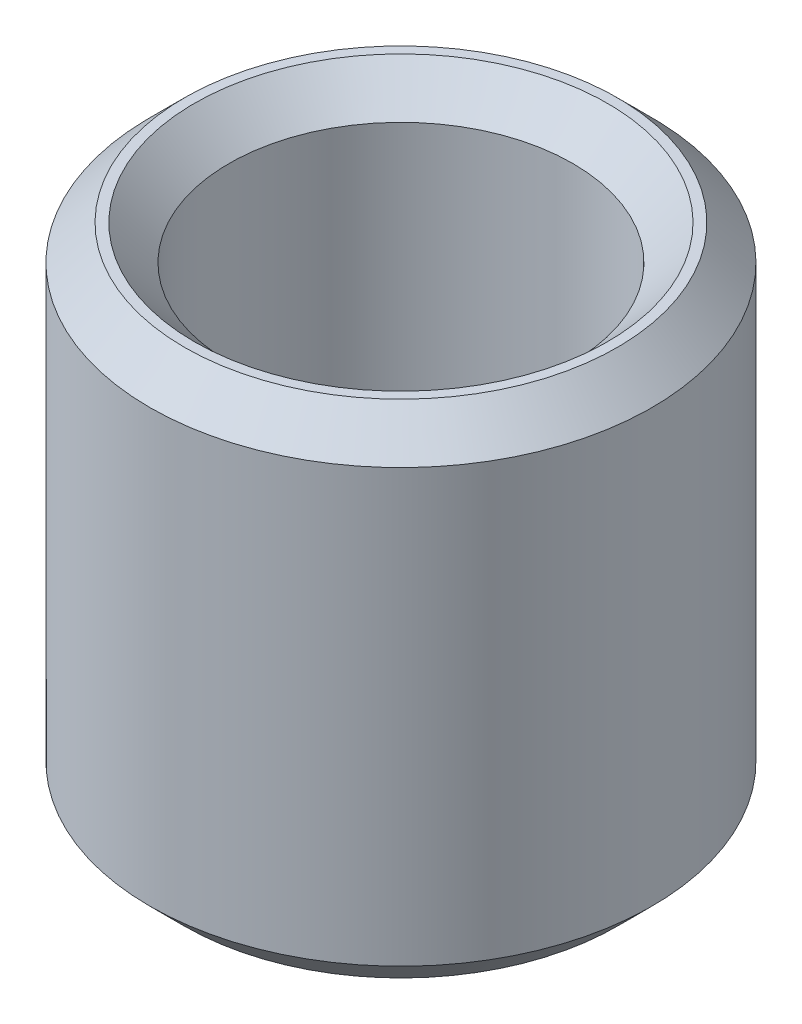
SolidWorks part; units mm, degrees
ref_plane "Front Plane" through (0, 0, 0) normal (0, 0, 1) x (1, 0, 0)
ref_plane "Top Plane" through (0, 0, 0) normal (0, 1, 0) x (1, 0, 0)
ref_plane "Right Plane" through (0, 0, 0) normal (1, 0, 0) x (0, 0, -1)
sketch "Sketch1" plane through (0, 0, 0) normal (0, 1, 0) x (1, 0, 0)
  circle A0 centre (0, 0) radius 25
  dimension "SLEEVE_OD" = 50
extrude "Boss-Extrude1" add sketch "Sketch1" along normal blind 49.9193
sketch "Sketch2" plane through (0, 0, 0) normal (0, 1, 0) x (1, 0, 0)
  circle A0 centre (0, 0) radius 17.1136
  dimension "BORE_D" = 34.2271
extrude "Cut-Extrude1" cut sketch "Sketch2" along normal through all
chamfer "Chamfer1" distance 3.4564 angle 45 4 edges at (0, 49.9193, 17.1136) (0, 0, 17.1136) (0, 0, 25) (0, 49.9193, 25)
